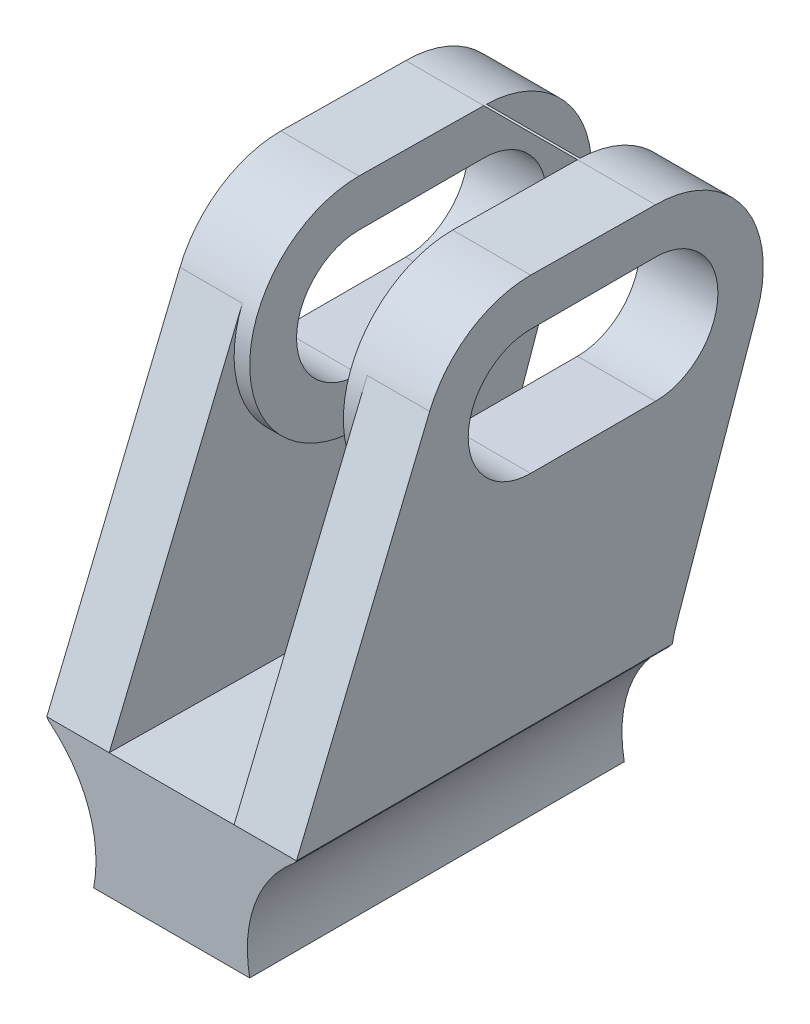
SolidWorks part; units mm, degrees
ref_plane "Front Plane" through (0, 0, 0) normal (0, 0, 1) x (1, 0, 0)
ref_plane "Top Plane" through (0, 0, 0) normal (0, 1, 0) x (1, 0, 0)
ref_plane "Right Plane" through (0, 0, 0) normal (1, 0, 0) x (0, 0, -1)
sketch "Sketch2" plane through (0, 0, 0) normal (0, 0, 1) x (1, 0, 0)
  line L0 (-15.875, 0) -> (15.875, 0)
  line L1 (0, 0) -> (0, 25.4) construction
  line L2 (25.4, 25.4) -> (-25.4, 25.4)
  arc A0 (24.6651, 24.5321) -> (15.875, 0) centre (40.7956, 4.9116) ccw
  arc A1 (24.6651, 24.5321) -> (25.4, 25.4) centre (22.6488, 26.9847) ccw
  arc A2 (-24.6651, 24.5321) -> (-25.4, 25.4) centre (-22.6488, 26.9847) cw
  arc A3 (-24.6651, 24.5321) -> (-15.875, 0) centre (-40.7956, 4.9116) cw
  dimension "D2" = 50.8
  dimension "D3" = 6.35
  dimension "D5" = 24.5321
  dimension "D1" = 15.875
  dimension "D4" = 25.4
  dimension "D6" = 25.4
extrude "Boss-Extrude1" add sketch "Sketch2" along normal blind 76.2
sketch "Sketch3" plane through (0, 0, 0) normal (1, 0, 0) x (0, 0, -1)
  line L0 (-15.875, 95.25) -> (-15.875, 69.85) construction
  line L2 (-76.2, 25.4) -> (0, 25.4) construction
  line L3 (0, 22.1539) -> (0, 13.7909)
  line L4 (0, 0) -> (0, 24.5321) construction
  line L5 (-28.575, 82.55) -> (-3.175, 82.55) construction
  line L6 (-28.575, 104.775) -> (-3.175, 104.4726)
  line L7 (-28.575, 95.25) -> (-3.175, 95.25)
  line L8 (-28.575, 69.85) -> (-3.175, 69.85)
  line L9 (-28.575, 60.325) -> (-3.175, 60.6274)
  line L11 (-76.2, 24.5321) -> (-76.2, 0) construction
  line L12 (-76.2, 25.4) -> (-49.1197, 91.0275)
  line L13 (1.075, 28.4629) -> (17.5105, 75.2897)
  line L14 (-76.2, 25.4) -> (-76.2, 24.5321)
  line L15 (-76.2, 24.5321) -> (0, 13.7909)
  line L16 (-76.2, 25.4) -> (0.2707, 25.3539)
  arc A0 (-28.575, 95.25) -> (-28.575, 69.85) centre (-28.575, 82.55) ccw
  arc A1 (-3.175, 69.85) -> (-3.175, 95.25) centre (-3.175, 82.55) ccw
  arc A2 (-28.575, 104.775) -> (-28.575, 60.325) centre (-28.575, 82.55) ccw
  arc A3 (0, 22.1539) -> (1.075, 28.4629) centre (19.05, 22.1539) cw
  arc A4 (-3.175, 60.6274) -> (-3.175, 104.4726) centre (-3.175, 82.55) ccw
  dimension "D4" = 25.4
  dimension "D5" = 25.4
  dimension "D6" = 44.45
  dimension "D7" = 25.4
  dimension "D8" = 0.682
  dimension "D10" = 21.9226
  dimension "D12" = 19.05
  dimension "D15" = 46.8269
  dimension "D1" = 57.15
  dimension "D2" = 60.325
  dimension "D3" = 25.4
  dimension "D11" = 25.4
  dimension "D13" = 76.9533
  dimension "D14" = 8.363
extrude "Boss-Extrude3" add sketch "Sketch3" along normal mid plane 50.8 contours L9 A4 L6 A2 A1 L8 A0 L7 | A4 L9 A2 L12 L16 A3 L13 region at (0, 45.2866, 32.4206) region at (0, 100.3351, 40.476)
sketch "Sketch4" plane through (0, 104.42, -1.2432) normal (0, 0.9999, -0.0119) x (1, 0, 0)
  line L0 (25.4, 17.7651) -> (-25.4, 17.7651) construction
  line L1 (-12.7, -76.497) -> (12.7, -76.497)
  line L2 (-12.7, -76.497) -> (-12.7, 17.7651)
  line L3 (-12.7, 17.7651) -> (12.7, 17.7651)
  line L4 (12.7, -76.497) -> (12.7, 17.7651)
  line L5 (25.4, -76.497) -> (-25.4, -76.497) construction
  line L6 (0, 17.7651) -> (0, -76.497) construction
  line L9 (-25.4, -17.1194) -> (0, -17.1194) construction
  line L10 (-25.4, -29.8203) -> (-25.4, -4.4185) construction
  line L11 (0, -17.1194) -> (25.4, -17.1194) construction
  line L12 (25.4, -29.8203) -> (25.4, -4.4185) construction
  point P14 (0, 17.7651)
  dimension "D1" = 25.4
extrude "Cut-Extrude1" cut sketch "Sketch4" against normal up to vertex (79.9363 mm away) up to point (25.4, 25.4, 76.2)
extrude "Boss-Extrude4" add sketch "Sketch3<7>" against normal blind 3.175 from offset 12.7 contours L9 A4 L6 A2 A1 L8 A0 L7 region at (0, 100.3351, 40.476)
sketch "Sketch3<7>" plane through (0, 0, 0) normal (1, 0, 0) x (0, 0, -1) same geometry as "Sketch3"
extrude "Boss-Extrude5" add sketch "Sketch3<8>" along normal blind 3.175 from offset 12.7 contours L9 A4 L6 A2 A1 L8 A0 L7 region at (0, 100.3351, 40.476) offset against normal yes
sketch "Sketch3<8>" plane through (0, 0, 0) normal (1, 0, 0) x (0, 0, -1) same geometry as "Sketch3"
sketch "Sketch5" plane through (0, 0, 0) normal (0, -1, 0) x (1, 0, 0)
  line L0 (0, 76.2) -> (0, 0) construction
  line L1 (-15.875, 76.2) -> (15.875, 76.2) construction
  circle A0 centre (0, 52.3875) radius 7.9375
  circle A1 centre (0, 23.8125) radius 7.9375
  dimension "D1" = 15.875
  dimension "D3" = 15.875
  dimension "D2" = 44.45
extrude "Cut-Extrude2" cut sketch "Sketch5" against normal blind 19.05
